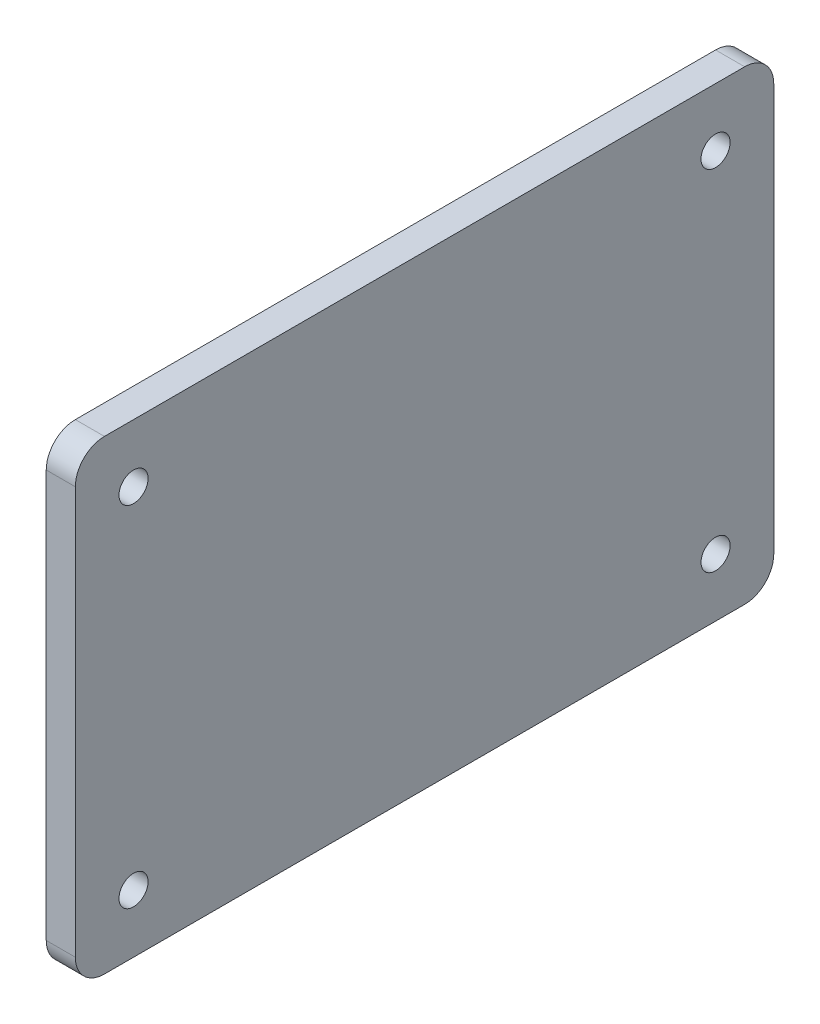
SolidWorks part; units mm, degrees
material "6061 Alloy"
ref_plane "Front Plane" through (0, 0, 0) normal (0, 0, 1) x (1, 0, 0)
ref_plane "Top Plane" through (0, 0, 0) normal (0, 1, 0) x (1, 0, 0)
ref_plane "Right Plane" through (0, 0, 0) normal (1, 0, 0) x (0, 0, -1)
sketch "Sketch1" plane through (-323.85, 0, 0) normal (-1, 0, 0) x (0, 0, 1)
  line L0 (-269.875, 120.65) -> (-415.925, 120.65) construction
  line L1 (-419.1, 120.65) -> (-266.7, 120.65)
  line L2 (-419.1, 120.65) -> (-419.1, 19.05)
  line L3 (-419.1, 19.05) -> (-266.7, 19.05)
  line L4 (-266.7, 120.65) -> (-266.7, 19.05)
  line L5 (-419.1, 117.475) -> (-419.1, 22.225) construction
  line L6 (-266.7, 22.225) -> (-266.7, 117.475) construction
  line L7 (-415.925, 19.05) -> (-269.875, 19.05) construction
extrude "Boss-Extrude1" add sketch "Sketch1" along normal blind 6.35
hole_wizard "1/4 (0.25) Diameter Hole1" positions "Sketch4" profile "Sketch3" hole size "1/4" standard "ANSI Inch" end condition through all
sketch "Sketch4" plane through (-330.2, 0, 0) normal (-1, 0, 0) x (0, 0, 1)
  line L0 (-419.1, 120.65) -> (-419.1, 19.05) construction
  line L1 (-419.1, 19.05) -> (-266.7, 19.05) construction
  point P0 (-406.4, 31.75)
  dimension "D1" = 12.7
  dimension "D2" = 12.7
sketch "Sketch3" plane through (-330.2, 31.75, -406.4) normal (0, 1, 0) x (0, 0, 1)
  line L0 (0, 0) -> (0, 6.35)
  line L1 (0, 6.35) -> (3.175, 6.35)
  line L2 (3.175, 6.35) -> (3.175, 0)
  line L5 (3.175, 0) -> (0, 0)
  line L11 (0, -6.35) -> (0, 107.95) construction
  dimension "Thru Hole Dia." = 6.35
  dimension "Thru Hole Depth" = 6.35
pattern_linear "LPattern1" count 2 spacing 76.2 along (0, 1, 0) count 2 spacing 127 along (0, 0, 1) of "1/4 (0.25) Diameter Hole1"
fillet "Fillet1" radius 6.35 4 edges at (-327.025, 120.65, -266.7) (-327.025, 19.05, -266.7) (-327.025, 19.05, -419.1) (-327.025, 120.65, -419.1)
